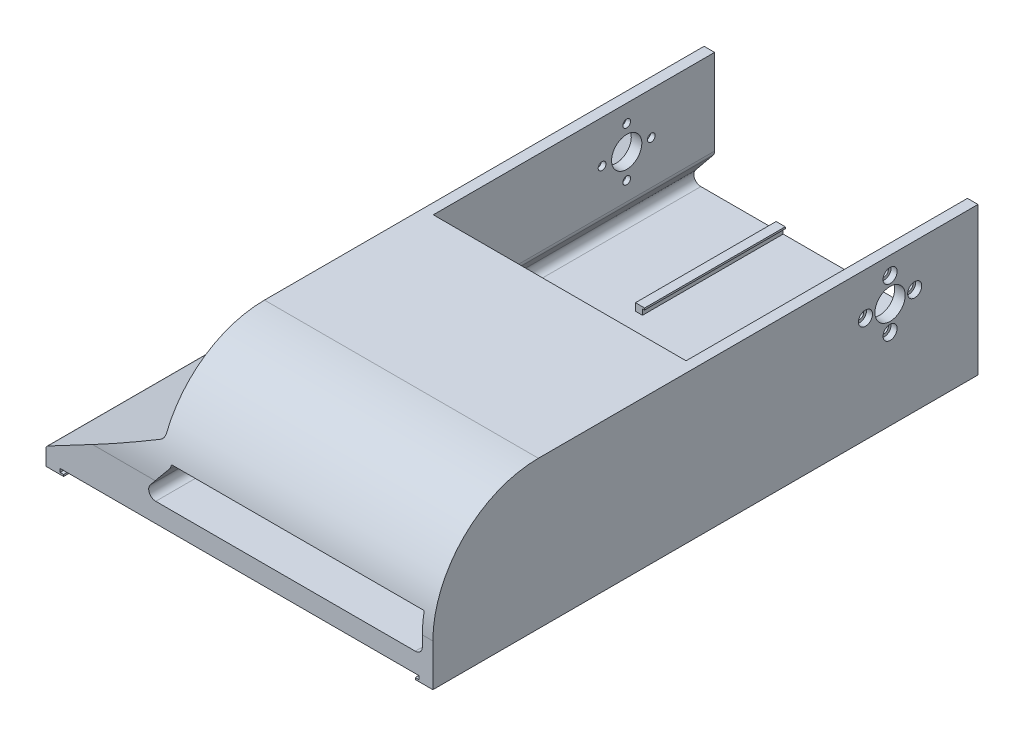
SolidWorks part; units mm, degrees
ref_plane "Front Plane" through (0, 0, 0) normal (0, 0, 1) x (1, 0, 0)
ref_plane "Top Plane" through (0, 0, 0) normal (0, 1, 0) x (1, 0, 0)
ref_plane "Right Plane" through (0, 0, 0) normal (1, 0, 0) x (0, 0, -1)
sketch "Sketch1" plane through (0, 0, 0) normal (0, 0, 1) x (1, 0, 0)
  line L0 (29.817, 42) -> (29.817, 17)
  line L1 (29.817, 42) -> (26.817, 42)
  line L2 (26.817, 42) -> (26.817, 22)
  line L4 (101.7033, 42) -> (104.7033, 42)
  line L5 (104.7033, 42) -> (104.7033, 14.3878)
  line L6 (104.7033, 14.3878) -> (104.7033, 0)
  line L7 (104.7033, 0) -> (99.7033, 0)
  line L8 (99.7033, 0) -> (99.7033, 0.5)
  line L9 (99.7033, 0.5) -> (100.7033, 0.5)
  line L10 (100.7033, 0.5) -> (100.7033, 1.5)
  line L11 (100.7033, 1.5) -> (-1.2967, 1.5)
  line L12 (-1.2967, 1.5) -> (-1.2967, 0.5)
  line L13 (-1.2967, 0.5) -> (-0.2967, 0.5)
  line L14 (-0.2967, 0.5) -> (-0.2967, 0)
  line L15 (-0.2967, 0) -> (-5.2967, 0)
  line L16 (-5.2967, 0) -> (-5.2967, 5)
  line L17 (-5.2967, 5) -> (26.817, 22)
  line L18 (29.817, 17) -> (21.7033, 7)
  line L21 (21.7033, 7) -> (101.7033, 7)
  line L22 (101.7033, 7) -> (101.7033, 42)
  line L23 (5.2469, 1.5) -> (5.2469, 1.35) construction
  line L24 (5.2469, 1.35) -> (15.2469, 1.35) construction
  line L25 (15.2469, 1.35) -> (15.2469, 1.5) construction
  line L26 (15.2469, 1.35) -> (15.2469, 1.147) construction
  line L27 (15.2469, 1.147) -> (5.2469, 1.147) construction
  line L28 (5.2469, 1.147) -> (5.2469, 1.35) construction
  dimension "D1" = 110
  dimension "D2" = 3
  dimension "D3" = 3
  dimension "D4" = 42
  dimension "D5" = 42
  dimension "D6" = 5
  dimension "D7" = 5
  dimension "D8" = 25
  dimension "D9" = 5
  dimension "D10" = 0.15
  dimension "D11" = 10
  dimension "D12" = 0.203
  dimension "D13" = 0.5
  dimension "D14" = 0.5
  dimension "D15" = 1
  dimension "D16" = 1
  dimension "D17" = 1
  dimension "D18" = 1
  dimension "D19" = 20
  dimension "D20" = 35
  dimension "D21" = 80
extrude "Boss-Extrude1" add sketch "Sketch1" along normal blind 155
sketch "Sketch2" plane through (29.817, 0, 0) normal (1, 0, 0) x (0, 0, -1)
  line L0 (-155, 42) -> (0, 42) construction
  line L1 (0, 17) -> (0, 42) construction
  circle A0 centre (-25, 30) radius 4.3
  circle A1 centre (-25, 37) radius 1.1
  circle A2 centre (-18, 30) radius 1.1
  circle A3 centre (-25, 23) radius 1.1
  circle A4 centre (-32, 30) radius 1.1
  dimension "D1" = 8.6
  dimension "D2" = 2.2
  dimension "D3" = 2.2
  dimension "D4" = 2.2
  dimension "D5" = 2.2
  dimension "D6" = 7
  dimension "D7" = 7
  dimension "D8" = 7
  dimension "D9" = 7
  dimension "D10" = 12
  dimension "D11" = 25
sketch "Sketch3" plane through (101.7033, 0, 0) normal (-1, 0, 0) x (0, 0, 1)
  circle A0 centre (25, 30) radius 4.3
  circle A1 centre (25, 37) radius 1.2
  circle A2 centre (32, 30) radius 1.2
  circle A3 centre (25, 23) radius 1.2
  circle A4 centre (18, 30) radius 1.2
  dimension "D1" = 8.6
  dimension "D2" = 2.4
  dimension "D3" = 2.4
  dimension "D4" = 2.4
  dimension "D5" = 2.4
  dimension "D6" = 7
  dimension "D7" = 7
  dimension "D8" = 7
  dimension "D9" = 7
extrude "Cut-Extrude1" cut sketch "Sketch3" against normal up to surface (3 mm away) contours A0 | A3 | A4 | A1 | A2 up to face at (104.7033, 21, 77.5)
extrude "Cut-Extrude2" cut sketch "Sketch2" against normal through all contours A1 | A0 | A2 | A4 | A3
sketch "Sketch4" plane through (104.7033, 0, 0) normal (1, 0, 0) x (0, 0, -1)
  circle A0 centre (-32, 30) radius 2
  circle A1 centre (-25, 37) radius 2
  circle A2 centre (-18, 30) radius 2
  circle A3 centre (-25, 23) radius 2
  dimension "D1" = 4
  dimension "D2" = 4
  dimension "D3" = 4
  dimension "D4" = 4
extrude "Cut-Extrude3" cut sketch "Sketch4" against normal offset from surface (1.7 mm away) 1.3 up to face at (101.7033, 23, 26.2)
sketch "Sketch5" plane through (26.817, 0, 0) normal (-1, 0, 0) x (0, 0, 1)
  circle A0 centre (25, 23) radius 2
  circle A1 centre (32, 30) radius 2
  circle A2 centre (25, 37) radius 2
  circle A3 centre (18, 30) radius 2
  dimension "D1" = 4
  dimension "D2" = 4
  dimension "D3" = 4
  dimension "D4" = 4
extrude "Cut-Extrude4" cut sketch "Sketch5" against normal offset from surface (1.7 mm away) 1.3 up to face at (29.817, 38.1, 25)
extrude "Cut-Extrude5" cut sketch "Sketch5<4>" along normal through all from surface starting at face at (28.517, 21, 25)
sketch "Sketch5<4>" plane through (26.817, 0, 0) normal (-1, 0, 0) x (0, 0, 1) same geometry as "Sketch5"
fillet "Fillet1" radius 2 5 edges at (101.7033, 7, 77.5) (29.817, 17, 77.5) (21.7033, 7, 77.5) (26.817, 22, 11.634) (26.817, 22, 90.866)
fillet "Fillet2" radius 1 1 edges at (-5.2967, 5, 77.5)
sketch "Sketch8" plane through (29.817, 0, 0) normal (1, 0, 0) x (0, 0, -1)
  line L0 (-155, 42) -> (-155, 17.7093)
  line L1 (-155, 17.7093) -> (-145, 17.7093)
  line L3 (-80, 32) -> (-80, 42)
  line L4 (-155, 42) -> (0, 42) construction
  line L5 (-80, 42) -> (-155, 42)
  arc A0 (-145, 17.7093) -> (-80, 32) centre (-103.4473, -16.321) cw
  dimension "D1" = 75
  dimension "D2" = 10
  dimension "D3" = 10
extrude "Boss-Extrude3" add sketch "Sketch8" along normal up to surface (71.8863 mm away) contours L1 A0 L3 L5 L0 up to face at (101.7033, 23, 26.2)
fillet "Fillet3" radius 30 1 edges at (65.7601, 42, 155)
sketch "Sketch10" plane through (0, 0, 0) normal (0, 0, -1) x (-1, 0, 0)
  line L0 (-74.7033, 7) -> (-74.7033, 8.6)
  line L1 (-99.7033, 7) -> (-25.9015, 7) construction
  line L2 (-74.7033, 8.6) -> (-74.1033, 8.6)
  line L3 (-74.1033, 8.6) -> (-74.1033, 9.1)
  line L4 (-74.1033, 9.1) -> (-76.7033, 9.1)
  line L5 (-76.7033, 9.1) -> (-76.7033, 7)
  line L6 (-76.7033, 7) -> (-74.7033, 7)
  line L7 (-47.3033, 7) -> (-47.3033, 9.1)
  line L8 (-47.3033, 9.1) -> (-49.9033, 9.1)
  line L9 (-49.9033, 9.1) -> (-49.9033, 8.6)
  line L10 (-49.9033, 8.6) -> (-49.3033, 8.6)
  line L11 (-49.3033, 8.6) -> (-49.3033, 7)
  line L12 (-49.3033, 7) -> (-47.3033, 7)
  line L13 (-101.7033, 42) -> (-101.7033, 9) construction
  dimension "D1" = 25.4
  dimension "D2" = 1.6
  dimension "D3" = 1.6
  dimension "D4" = 0.6
  dimension "D5" = 0.5
  dimension "D6" = 0.6
  dimension "D7" = 0.5
  dimension "D8" = 2
  dimension "D9" = 2
  dimension "D10" = 25
extrude "Boss-Extrude4" add sketch "Sketch10" against normal blind 40 contours L4 L5 L6 L0 L2 L3 | L8 L9 L10 L11 L12 L7
